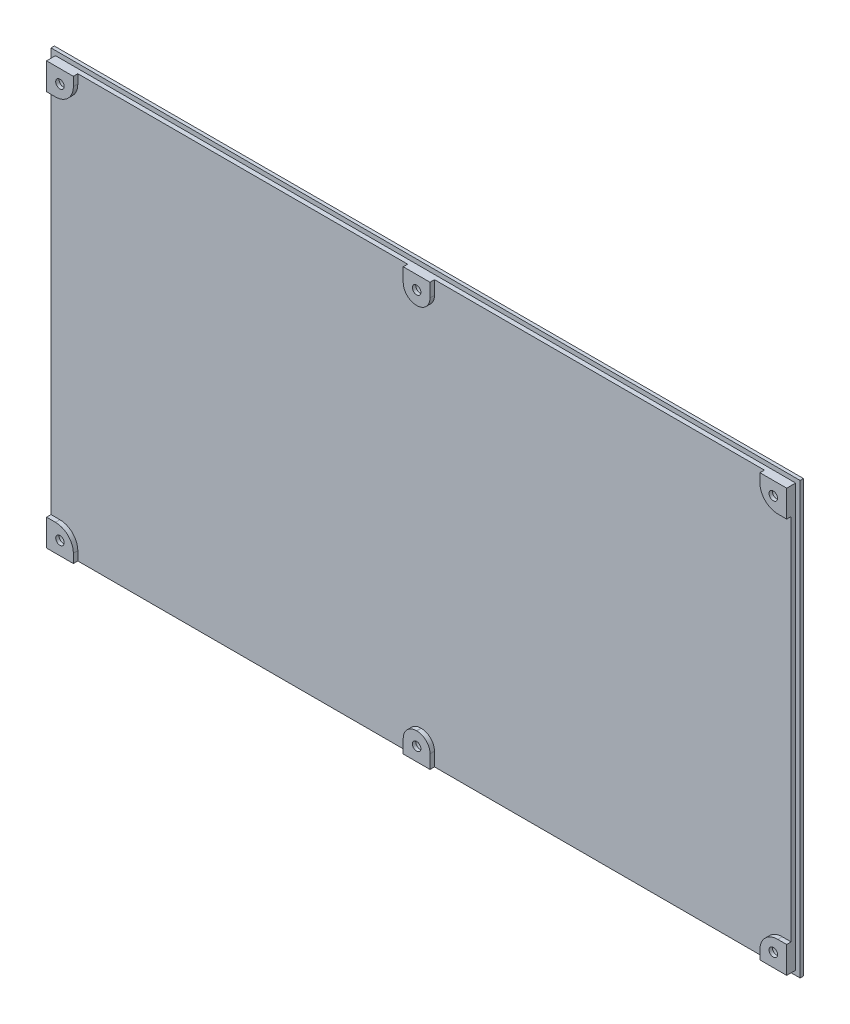
SolidWorks part; units mm, degrees
ref_plane "Front Plane" through (0, 0, 0) normal (0, 0, 1) x (1, 0, 0)
ref_plane "Top Plane" through (0, 0, 0) normal (0, 1, 0) x (1, 0, 0)
ref_plane "Right Plane" through (0, 0, 0) normal (1, 0, 0) x (0, 0, -1)
sketch "Sketch1" plane through (0, 0, 0) normal (0, 0, 1) x (1, 0, 0)
  line L1 (-167.75, -96.5) -> (167.75, -96.5)
  line L2 (-167.75, -96.5) -> (-167.75, 96.5)
  line L3 (-167.75, 96.5) -> (167.75, 96.5)
  line L4 (167.75, -96.5) -> (167.75, 96.5)
  line L5 (-167.75, -96.5) -> (167.75, 96.5) construction
  line L6 (-167.75, 96.5) -> (167.75, -96.5) construction
  point P0 (0, 0)
  dimension "D1" = 193
  dimension "D2" = 335.5
extrude "Boss-Extrude1" add sketch "Sketch1" along normal blind 1.5
sketch "Sketch2" plane through (0, 0, 1.5) normal (0, 0, 1) x (1, 0, 0)
  line L0 (167.75, 96.5) -> (-167.75, 96.5) construction
  line L1 (-165.75, -94.5) -> (165.75, -94.5)
  line L2 (-165.75, -94.5) -> (-165.75, 94.5)
  line L3 (-165.75, 94.5) -> (165.75, 94.5)
  line L4 (165.75, -94.5) -> (165.75, 94.5)
  line L5 (-165.75, -94.5) -> (165.75, 94.5) construction
  line L6 (-165.75, 94.5) -> (165.75, -94.5) construction
  line L7 (-167.75, 96.5) -> (-167.75, -96.5) construction
  line L8 (-153.75, -82.5) -> (-153.75, 82.5) construction
  line L9 (-165.75, 94.5) -> (-153.75, 94.5)
  line L10 (-165.75, 94.5) -> (-165.75, 82.5)
  line L11 (-165.75, 82.5) -> (-161.75, 82.5)
  line L12 (-153.75, 94.5) -> (-153.75, 90.5)
  line L13 (165.75, 94.5) -> (153.75, 94.5)
  line L14 (165.75, 94.5) -> (165.75, 82.5)
  line L15 (165.75, 82.5) -> (161.75, 82.5)
  line L16 (153.75, 94.5) -> (153.75, 90.5)
  line L17 (165.75, -94.5) -> (153.75, -94.5)
  line L18 (165.75, -94.5) -> (165.75, -82.5)
  line L19 (165.75, -82.5) -> (161.75, -82.5)
  line L20 (153.75, -94.5) -> (153.75, -90.5)
  line L21 (-165.75, -94.5) -> (-153.75, -94.5)
  line L22 (-165.75, -94.5) -> (-165.75, -82.5)
  line L23 (-165.75, -82.5) -> (-161.75, -82.5)
  line L24 (-153.75, -94.5) -> (-153.75, -90.5)
  line L25 (-153.75, 82.5) -> (153.75, 82.5) construction
  line L26 (153.75, 82.5) -> (153.75, -82.5) construction
  line L27 (153.75, -82.5) -> (-153.75, -82.5) construction
  line L28 (0, 94.5) -> (0, -94.5) construction
  line L30 (0.1, 82.5) -> (-0.1, 82.5)
  line L31 (6, 88.4) -> (6, 94.5)
  line L32 (6, 94.5) -> (-6, 94.5)
  line L33 (-6, 88.4) -> (-6, 94.5)
  line L34 (6, 82.5) -> (-6, 94.5) construction
  line L35 (6, 94.5) -> (-6, 82.5) construction
  line L36 (0.1, -82.5) -> (-0.1, -82.5)
  line L37 (6, -88.4) -> (6, -94.5)
  line L38 (6, -94.5) -> (-6, -94.5)
  line L39 (-6, -88.4) -> (-6, -94.5)
  line L40 (6, -82.5) -> (-6, -94.5) construction
  line L41 (6, -94.5) -> (-6, -82.5) construction
  arc A0 (161.75, 82.5) -> (153.75, 90.5) centre (161.75, 90.5) cw
  arc A1 (161.75, -82.5) -> (153.75, -90.5) centre (161.75, -90.5) ccw
  arc A2 (-161.75, -82.5) -> (-153.75, -90.5) centre (-161.75, -90.5) cw
  arc A3 (-161.75, 82.5) -> (-153.75, 90.5) centre (-161.75, 90.5) ccw
  arc A4 (-0.1, -82.5) -> (-6, -88.4) centre (-0.1, -88.4) ccw
  arc A5 (0.1, -82.5) -> (6, -88.4) centre (0.1, -88.4) cw
  arc A6 (0.1, 82.5) -> (6, 88.4) centre (0.1, 88.4) ccw
  arc A7 (-0.1, 82.5) -> (-6, 88.4) centre (-0.1, 88.4) cw
  point P0 (0, 0)
  point P24 (0, 88.5)
  point P29 (0, -88.5)
  dimension "D9" = 8
  dimension "D10" = 5.9
  dimension "D1" = 2
  dimension "D2" = 2
  dimension "D3" = 12
  dimension "D4" = 12
  dimension "D5" = 12
  dimension "D6" = 12
  dimension "D7" = 12
  dimension "D8" = 12
extrude "Boss-Extrude2" add sketch "Sketch2" along normal blind 2 contours L30 A7 L33 L3 L12 A3 L11 L2 L23 A2 L24 L1 L39 A4 L36 A5 L37 L20 A1 L19 L4 L15 A0 L16 L31 A6 region at (0, 0, 1.5)
sketch "Sketch4" plane through (0, 0, 1.5) normal (0, 0, 1) x (1, 0, 0)
  line L0 (-165.75, -82.5) -> (-165.75, -94.5)
  line L1 (-165.75, -94.5) -> (-153.75, -94.5)
  line L2 (-165.75, -82.5) -> (-161.75, -82.5) construction
  line L3 (-153.75, -94.5) -> (-153.75, -90.5) construction
  line L4 (-6, -88.4) -> (-6, -94.5) construction
  line L5 (6, -88.4) -> (6, -94.5) construction
  line L6 (0.1, -82.5) -> (-0.1, -82.5) construction
  line L7 (153.75, -94.5) -> (153.75, -90.5) construction
  line L8 (165.75, -82.5) -> (161.75, -82.5) construction
  line L9 (165.75, 82.5) -> (161.75, 82.5) construction
  line L10 (153.75, 94.5) -> (153.75, 90.5) construction
  line L11 (6, 88.4) -> (6, 94.5) construction
  line L12 (-6, 88.4) -> (-6, 94.5) construction
  line L13 (0.1, 82.5) -> (-0.1, 82.5) construction
  line L14 (-165.75, 82.5) -> (-161.75, 82.5) construction
  line L15 (-153.75, 94.5) -> (-153.75, 90.5) construction
  line L16 (-165.75, -82.5) -> (-161.75, -82.5)
  line L17 (-153.75, -94.5) -> (-153.75, -90.5)
  line L18 (-6, -88.4) -> (-6, -94.5)
  line L19 (6, -88.4) -> (6, -94.5)
  line L20 (0.1, -82.5) -> (-0.1, -82.5)
  line L21 (153.75, -94.5) -> (153.75, -90.5)
  line L22 (165.75, -82.5) -> (161.75, -82.5)
  line L23 (165.75, 82.5) -> (161.75, 82.5)
  line L24 (153.75, 94.5) -> (153.75, 90.5)
  line L25 (6, 88.4) -> (6, 94.5)
  line L26 (-6, 88.4) -> (-6, 94.5)
  line L27 (0.1, 82.5) -> (-0.1, 82.5)
  line L28 (-165.75, 82.5) -> (-161.75, 82.5)
  line L29 (-153.75, 94.5) -> (-153.75, 90.5)
  line L30 (-165.75, 82.5) -> (-165.75, 94.5)
  line L31 (-165.75, 94.5) -> (-153.75, 94.5)
  line L32 (-153.75, 94.5) -> (-153.6464, 89.5179)
  line L33 (-6, 94.5) -> (6, 94.5)
  line L34 (153.75, 94.5) -> (165.75, 94.5)
  line L35 (165.75, 94.5) -> (165.75, 82.5)
  line L36 (153.75, -94.5) -> (165.75, -94.5)
  line L37 (165.75, -94.5) -> (165.75, -82.5)
  line L38 (-6, -94.5) -> (6, -94.5)
  arc A0 (-153.75, -90.5) -> (-161.75, -82.5) centre (-161.75, -90.5) ccw construction
  arc A1 (-0.1, -82.5) -> (-6, -88.4) centre (-0.1, -88.4) ccw construction
  arc A2 (6, -88.4) -> (0.1, -82.5) centre (0.1, -88.4) ccw construction
  arc A3 (161.75, -82.5) -> (153.75, -90.5) centre (161.75, -90.5) ccw construction
  arc A4 (153.75, 90.5) -> (161.75, 82.5) centre (161.75, 90.5) ccw construction
  arc A5 (0.1, 82.5) -> (6, 88.4) centre (0.1, 88.4) ccw construction
  arc A6 (-6, 88.4) -> (-0.1, 82.5) centre (-0.1, 88.4) ccw construction
  arc A7 (-161.75, 82.5) -> (-153.75, 90.5) centre (-161.75, 90.5) ccw construction
  arc A8 (-153.75, -90.5) -> (-161.75, -82.5) centre (-161.75, -90.5) ccw
  arc A9 (-0.1, -82.5) -> (-6, -88.4) centre (-0.1, -88.4) ccw
  arc A10 (6, -88.4) -> (0.1, -82.5) centre (0.1, -88.4) ccw
  arc A11 (161.75, -82.5) -> (153.75, -90.5) centre (161.75, -90.5) ccw
  arc A12 (153.75, 90.5) -> (161.75, 82.5) centre (161.75, 90.5) ccw
  arc A13 (0.1, 82.5) -> (6, 88.4) centre (0.1, 88.4) ccw
  arc A14 (-6, 88.4) -> (-0.1, 82.5) centre (-0.1, 88.4) ccw
  arc A15 (-161.75, 82.5) -> (-153.75, 90.5) centre (-161.75, 90.5) ccw
  line M2 (-0.1, 82.5) -> (0.1, 82.5)
  arc M3 (0.1, 82.5) -> (6, 88.4) centre (0.1, 88.4) ccw
  line M4 (6, 88.4) -> (6, 94.5)
  line M6 (153.75, 94.5) -> (153.75, 90.5)
  arc M7 (153.75, 90.5) -> (161.75, 82.5) centre (161.75, 90.5) ccw
  line M8 (161.75, 82.5) -> (165.75, 82.5)
  line M10 (165.75, -82.5) -> (161.75, -82.5)
  arc M11 (161.75, -82.5) -> (153.75, -90.5) centre (161.75, -90.5) ccw
  line M12 (153.75, -90.5) -> (153.75, -94.5)
  line M14 (6, -94.5) -> (6, -88.4)
  arc M15 (6, -88.4) -> (0.1, -82.5) centre (0.1, -88.4) ccw
  line M16 (0.1, -82.5) -> (-0.1, -82.5)
  arc M17 (-0.1, -82.5) -> (-6, -88.4) centre (-0.1, -88.4) ccw
  line M18 (-6, -88.4) -> (-6, -94.5)
  line M20 (-153.75, -94.5) -> (-153.75, -90.5)
  arc M21 (-153.75, -90.5) -> (-161.75, -82.5) centre (-161.75, -90.5) ccw
  line M22 (-161.75, -82.5) -> (-165.75, -82.5)
  line M28 (-6, 94.5) -> (-6, 88.4)
  arc M29 (-6, 88.4) -> (-0.1, 82.5) centre (-0.1, 88.4) ccw
extrude "Boss-Extrude3" add sketch "Sketch4" along normal blind 4 contours L0 L1 M20 M21 M22 | L38 M18 M14 M15 M16 M17 | L36 L37 M10 M11 M12 | L35 L34 M6 M7 M8 | L33 M28 M29 M2 M3 M4 | L29 A15 L28 L30 L31 region at (-160.1942, -88.9442, 1.5) region at (0, -89.042, 1.5) region at (160.1942, -88.9442, 1.5) region at (160.1942, 88.9442, 1.5) region at (0, 89.042, 1.5)
sketch "Sketch5" plane through (0, 0, 0) normal (0, 0, -1) x (-1, 0, 0)
  line L0 (-167.75, 88.5) -> (167.75, 88.5) construction
  line L1 (-167.75, -96.5) -> (-167.75, 96.5) construction
  line L2 (167.75, 96.5) -> (167.75, -96.5) construction
  line L3 (-167.75, -88.5) -> (167.75, -88.5) construction
  line L4 (-167.75, 96.5) -> (167.75, 96.5) construction
  line L5 (167.75, -96.5) -> (-167.75, -96.5) construction
  circle A0 centre (-159.75, 88.5) radius 4
  circle A1 centre (0, 88.5) radius 4
  circle A2 centre (0, -88.5) radius 4
  circle A3 centre (159.75, 88.5) radius 4
  circle A4 centre (159.75, -88.5) radius 4
  circle A5 centre (-159.75, -88.5) radius 4
  dimension "D3" = 8
  dimension "D4" = 8
  dimension "D5" = 8
  dimension "D1" = 8
  dimension "D2" = 8
  dimension "D6" = 8
  dimension "D7" = 8
extrude "Cut-Extrude1" cut sketch "Sketch5" against normal blind 4
sketch "Sketch6" plane through (0, 0, 0) normal (0, 0, -1) x (-1, 0, 0)
  circle A0 centre (-159.75, -88.5) radius 1.9
  circle A1 centre (0, -88.5) radius 1.9
  circle A2 centre (159.75, -88.5) radius 1.9
  circle A3 centre (159.75, 88.5) radius 1.9
  circle A4 centre (0, 88.5) radius 1.9
  circle A5 centre (-159.75, 88.5) radius 1.9
  dimension "D1" = 3.8
extrude "Cut-Extrude2" cut sketch "Sketch6" against normal blind 14
